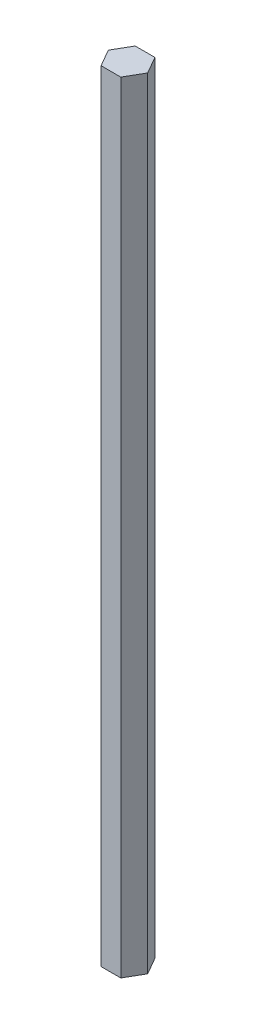
SolidWorks part; units mm, degrees
material "6061-T6 (SS)"
ref_plane "Front" through (0, 0, 0) normal (0, 0, 1) x (1, 0, 0)
ref_plane "Top" through (0, 0, 0) normal (0, 1, 0) x (1, 0, 0)
ref_plane "Right" through (0, 0, 0) normal (1, 0, 0) x (0, 0, -1)
sketch "Sketch1" plane through (0, 0, 0) normal (0, 1, 0) x (1, 0, 0)
  line L1 (2.8868, 0) -> (1.4434, 2.5)
  line L2 (1.4434, 2.5) -> (-1.4434, 2.5)
  line L3 (-1.4434, 2.5) -> (-2.8868, 0)
  line L4 (-2.8868, 0) -> (-1.4434, -2.5)
  line L5 (-1.4434, -2.5) -> (1.4434, -2.5)
  line L6 (1.4434, -2.5) -> (2.8868, 0)
  circle A0 centre (0, 0) radius 2.5 construction
  dimension "D1" = 5
extrude "Boss-Extrude1" add sketch "Sketch1" along normal mid plane 114.3
ref_axis "Axis1" through (0, 49.5981, 0) along (0, -1, 0)
